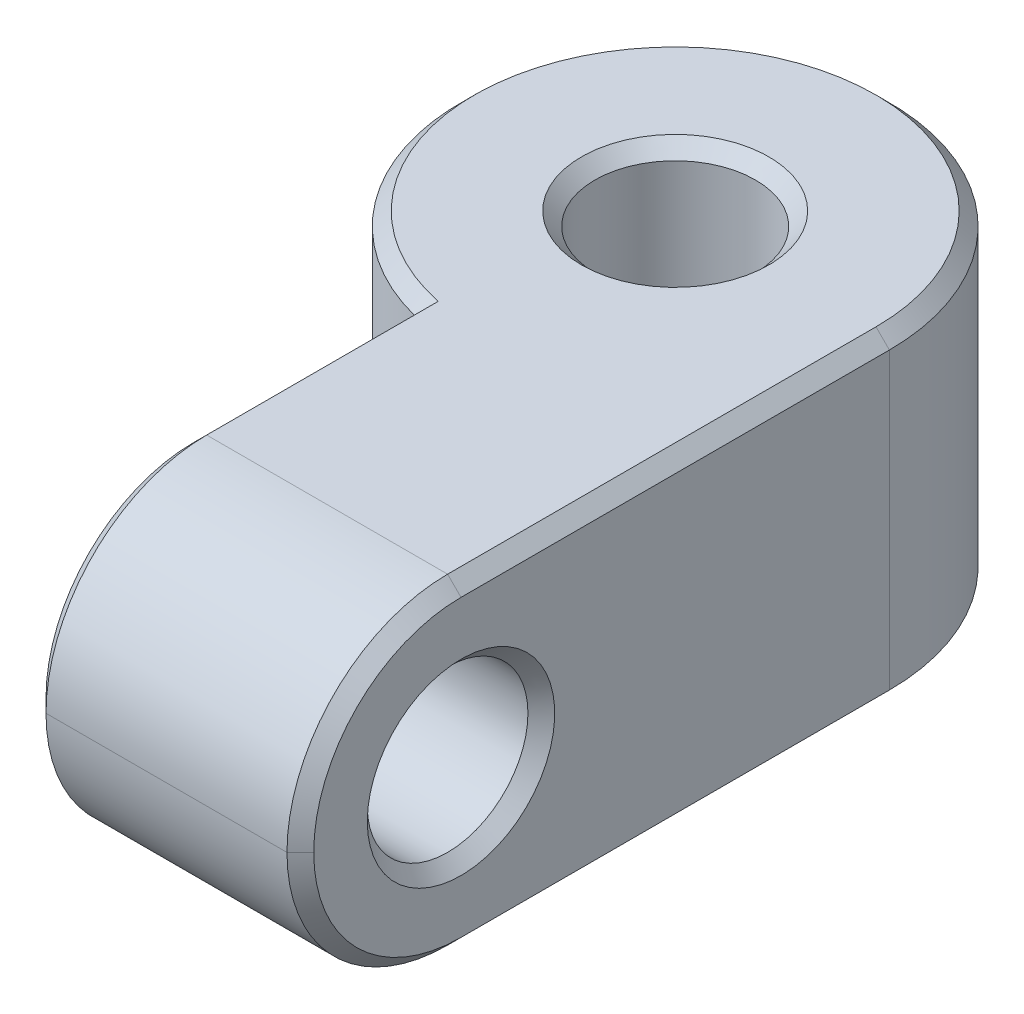
SolidWorks part; units mm, degrees
ref_plane "Front Plane" through (0, 0, 0) normal (0, 0, 1) x (1, 0, 0)
ref_plane "Top Plane" through (0, 0, 0) normal (0, 1, 0) x (1, 0, 0)
ref_plane "Right Plane" through (0, 0, 0) normal (1, 0, 0) x (0, 0, -1)
sketch "Sketch1" plane through (0, 0, 0) normal (0, 1, 0) x (1, 0, 0)
  line L0 (-1.5875, -17.4625) -> (-1.5875, -6.1484)
  line L5 (-1.5875, -17.4625) -> (6.35, -17.4625)
  line L6 (6.35, -17.4625) -> (6.35, 0)
  circle A0 centre (0, 0) radius 2.3813
  arc A1 (6.35, 0) -> (-1.5875, -6.1484) centre (0, 0) ccw
  dimension "D1" = 4.7625
  dimension "D2" = 12.7
  dimension "D3" = 1.5875
  dimension "D4" = 17.4625
extrude "Boss-Extrude1" add sketch "Sketch1" along normal blind 9.525
sketch "Sketch5" plane through (6.35, 0, 0) normal (1, 0, 0) x (0, 0, -1)
  line L0 (-17.4625, 0) -> (0, 0) construction
  circle A0 centre (-12.7, 4.7625) radius 2.3813
  dimension "D3" = 4.7625
  dimension "D1" = 12.7
  dimension "D2" = 4.7625
extrude "Cut-Extrude3" cut sketch "Sketch5" against normal through all both and the other way through all
fillet "Fillet1" radius 4.7625 2 edges at (2.3812, 0, 17.4625) (2.3812, 9.525, 17.4625)
chamfer "Chamfer1" distance 0.3969 angle 45 13 edges at (6.35, 4.7625, 15.0812) (-1.5875, 4.7625, 10.3187) (0, 9.525, 2.3813) (-3.8886, 0, -5.0201) (6.35, 0, 6.35) (-1.5875, 0, 9.4242) (6.35, 1.3949, 16.0676) (-1.5875, 1.3949, 16.0676) (6.35, 8.1301, 16.0676) (-1.5875, 8.1301, 16.0676) (6.35, 9.525, 6.35) (-3.8886, 9.525, -5.0201) (-1.5875, 9.525, 9.4242)
